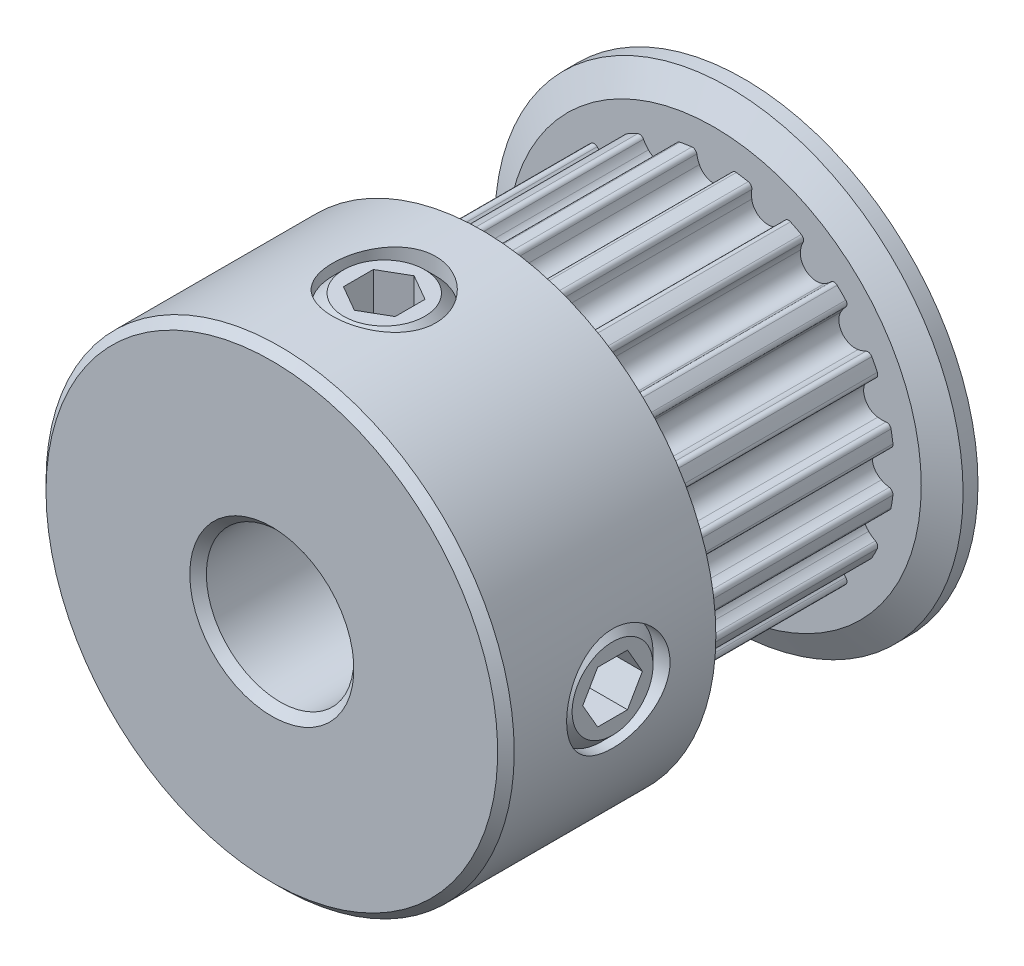
SolidWorks part; units mm, degrees
ref_plane "Front Plane" through (0, 0, 0) normal (0, 0, 1) x (1, 0, 0)
ref_plane "Top Plane" through (0, 0, 0) normal (0, 1, 0) x (1, 0, 0)
ref_plane "Right Plane" through (0, 0, 0) normal (1, 0, 0) x (0, 0, -1)
sketch "Sketch1" plane through (0, 0, 0) normal (0, 0, 1) x (1, 0, 0)
  line L1 (-1.7499, 5.3585) -> (1.7499, 5.3585) construction
  line L4 (0, 0) -> (0, 5.3585) construction
  line L5 (0, 5.3585) -> (0, 11.2111) construction
  line L6 (0, 6.3625) -> (1.9751, 6.0482) construction
  line L7 (1.9751, 6.0482) -> (2.6648, 5.8229) construction
  line L8 (1.9751, 6.0482) -> (1.7499, 5.3585) construction
  line L9 (-1.9751, 6.0482) -> (-1.7499, 5.3585) construction
  line L10 (-1.8963, 5.8067) -> (-2.5913, 7.935)
  line L11 (-2.5913, 7.935) -> (2.5913, 7.935)
  line L12 (2.5913, 7.935) -> (1.8963, 5.8067)
  circle A0 centre (0, 0) radius 6.3625 construction
  circle A1 centre (0, 0) radius 7.935 construction
  circle A2 centre (0, 0) radius 6.1085 construction
  arc A3 (-0.4989, 5.6703) -> (0.4989, 5.6703) centre (0, 5.9135) ccw
  arc A4 (-0.4989, 5.6703) -> (-0.5855, 5.9387) centre (0.4, 6.1085) cw
  arc A5 (-1.8963, 5.8067) -> (-0.7518, 6.0621) centre (0, 0) cw
  arc A6 (-0.5855, 5.9387) -> (-0.7518, 6.0621) centre (-0.7333, 5.9132) ccw
  arc A7 (1.8963, 5.8067) -> (0.7518, 6.0621) centre (0, 0) ccw
  arc A8 (0.5855, 5.9387) -> (0.7518, 6.0621) centre (0.7333, 5.9132) cw
  arc A9 (0.4989, 5.6703) -> (0.5855, 5.9387) centre (-0.4, 6.1085) ccw
  point P6 (0, 20.9083)
  point P11 (0, 6.3625)
  point P13 (0, 7.935)
  point P14 (0, 6.1085)
  dimension "D1" = 9.6972
  dimension "D2" = 4.8486
sketch "Sketch2" plane through (0, 0, 0) normal (1, 0, 0) x (0, 0, -1)
  line L0 (-8, 2.5) -> (8, 2.5)
  line L1 (-8, 2.5) -> (-8, 7.935)
  line L2 (-0.885, 7.935) -> (-8, 7.935)
  line L3 (-1.39, 2.5) -> (-1.39, 7.935) construction
  line L4 (-1.39, 7.935) -> (-0.38, 7.935) construction
  line L5 (-0.38, 7.935) -> (-0.38, 6.1085) construction
  line L6 (-0.38, 6.1085) -> (6.99, 6.1085)
  line L7 (6.99, 6.1085) -> (6.99, 7.935) construction
  line L8 (6.99, 7.935) -> (8, 7.935) construction
  line L9 (8, 7.935) -> (8, 2.5)
  line L10 (-8, 0) -> (8, 0) construction
  line L11 (7.495, 7.935) -> (6.99, 7.0217)
  line L12 (-0.38, 7.0217) -> (-0.885, 7.935)
  line L14 (-0.38, 7.0217) -> (-0.38, 6.1085)
  line L15 (6.99, 6.1085) -> (6.99, 7.0217)
  line L16 (7.495, 7.935) -> (8, 7.935)
  arc A0 (-0.38, 7.0217) -> (-0.885, 7.935) centre (-1.4583, 7.0217) ccw construction
  arc A1 (6.99, 7.0217) -> (7.495, 7.935) centre (8.0683, 7.0217) cw construction
  point P12 (-0.38, 7.0217)
  point P14 (-0.885, 7.935)
  point P20 (6.99, 7.0217)
  point P21 (7.495, 7.935)
  point P25 (6.99, 0)
  point P26 (-0.38, 0)
  dimension "OA" = 16
  dimension "Bore" = 5
  dimension "Outside Width" = 8.38
  dimension "Inside Width" = 7.37
revolve "Revolve1" add sketch "Sketch2" angle 360 mid plane about L10
sketch "Sketch3" plane through (0, 0, 0) normal (0, 0, 1) x (1, 0, 0)
  line L6 (2.5913, 7.935) -> (-2.5913, 7.935)
  line L7 (1.8963, 5.8067) -> (2.5913, 7.935)
  line L8 (-2.5913, 7.935) -> (-1.8963, 5.8067)
  line L9 (2.5913, 7.935) -> (-2.5913, 7.935)
  line L10 (1.8963, 5.8067) -> (2.5913, 7.935)
  line L11 (-2.5913, 7.935) -> (-1.8963, 5.8067)
  arc A8 (1.8963, 5.8067) -> (0.7518, 6.0621) centre (0, 0) ccw
  arc A9 (0.7518, 6.0621) -> (0.5855, 5.9387) centre (0.7333, 5.9132) ccw
  arc A10 (0.4989, 5.6703) -> (0.5855, 5.9387) centre (-0.4, 6.1085) ccw
  arc A11 (-0.4989, 5.6703) -> (0.4989, 5.6703) centre (0, 5.9135) ccw
  arc A12 (-0.5855, 5.9387) -> (-0.4989, 5.6703) centre (0.4, 6.1085) ccw
  arc A13 (-0.5855, 5.9387) -> (-0.7518, 6.0621) centre (-0.7333, 5.9132) ccw
  arc A14 (-0.7518, 6.0621) -> (-1.8963, 5.8067) centre (0, 0) ccw
  arc A15 (1.8963, 5.8067) -> (0.7518, 6.0621) centre (0, 0) ccw
  arc A16 (0.7518, 6.0621) -> (0.5855, 5.9387) centre (0.7333, 5.9132) ccw
  arc A17 (0.4989, 5.6703) -> (0.5855, 5.9387) centre (-0.4, 6.1085) ccw
  arc A18 (-0.4989, 5.6703) -> (0.4989, 5.6703) centre (0, 5.9135) ccw
  arc A19 (-0.5855, 5.9387) -> (-0.4989, 5.6703) centre (0.4, 6.1085) ccw
  arc A20 (-0.5855, 5.9387) -> (-0.7518, 6.0621) centre (-0.7333, 5.9132) ccw
  arc A21 (-0.7518, 6.0621) -> (-1.8963, 5.8067) centre (0, 0) ccw
  dimension "D1" = 0
extrude "Cut-Extrude1" cut sketch "Sketch3" against normal up to vertex (6.99 mm away) from vertex up to point (0, 6.1085, -6.99) starting at point (0, 6.1085, 0.38)
pattern_circular "CirPattern1" count 20 over 360 about axis through (0, 0, 8) along (0, 0, 1) of "Cut-Extrude1"
sketch "Sketch4" plane through (0, 0, 0) normal (1, 0, 0) x (0, -1, 0)
  line L0 (0, -0.38) -> (0, -8) construction
  line L1 (-2.5, -8) -> (2.5, -8) construction
  line L2 (7.0217, -0.38) -> (-7.0217, -0.38) construction
  circle A0 centre (0, -4.19) radius 1.7526
extrude "Cut-Extrude2" cut sketch "Sketch4" along normal through all
ref_plane "Plane1" through (0, 0, 4.19) normal (0, 0, 1) x (1, 0, 0)
sketch "Sketch5" plane through (0, 0, 4.19) normal (0, 0, 1) x (1, 0, 0)
  line L0 (0, 0) -> (0, 7.935) construction
  line L1 (2.5, -1.3716) -> (2.5, 0)
  line L2 (2.881, -1.7526) -> (7.358, -1.7526)
  line L3 (2.5, 0) -> (7.935, 0) construction
  line L4 (2.5, 0) -> (7.739, 0)
  line L5 (7.739, 0) -> (7.739, -1.3716)
  line L6 (2.881, -1.7526) -> (2.5, -1.3716)
  line L7 (7.739, -1.3716) -> (7.358, -1.7526)
  circle A0 centre (0, 0) radius 7.935 construction
  circle A1 centre (0, 0) radius 2.5 construction
  point P2 (2.5, -1.7526)
  point P11 (7.739, -1.7526)
revolve "Revolve2" add sketch "Sketch5" angle 360 mid plane about L4
sketch "Sketch6" plane through (7.739, 5.3841, 0) normal (-1, 0, 0) x (0, -1, 0)
  line L1 (5.3841, 5.2019) -> (4.5078, 4.6959)
  line L2 (4.5078, 4.6959) -> (4.5078, 3.6841)
  line L3 (4.5078, 3.6841) -> (5.3841, 3.1781)
  line L4 (5.3841, 3.1781) -> (6.2604, 3.6841)
  line L5 (6.2604, 3.6841) -> (6.2604, 4.6959)
  line L6 (6.2604, 4.6959) -> (5.3841, 5.2019)
  circle A0 centre (5.3841, 4.19) radius 0.8763 construction
  dimension "D1" = 1.7526
extrude "Cut-Extrude3" cut sketch "Sketch6" along normal blind 1.3144
pattern_circular "CirPattern3" count 2 over 90 about axis through (0, 0, 8) along (0, 0, 1) of "Cut-Extrude2", "Revolve2", "Cut-Extrude3"
chamfer "Chamfer1" distance 0.2807 angle 45 2 edges at (2.5, 0, 8) (7.935, 0, 8)
ref_axis "Center Axis 1" through (0, 0, -8) along (0, 0, 1)
ref_plane "Contact Plane 1" through (0, 0, 8) normal (0, 0, 1) x (1, 0, 0)
ref_plane "Contact Plane 2" through (0, 0, -8) normal (0, 0, -1) x (-1, 0, 0)
equation "\"D2@Sketch1\"= \"D1@Sketch1\" / 2"
equation "\"D1@Sketch6\" = \"Set Screw@Sketch4\" / 2"
equation "\"D1@Cut-Extrude3\" = \"D1@Sketch6\"*.75"
